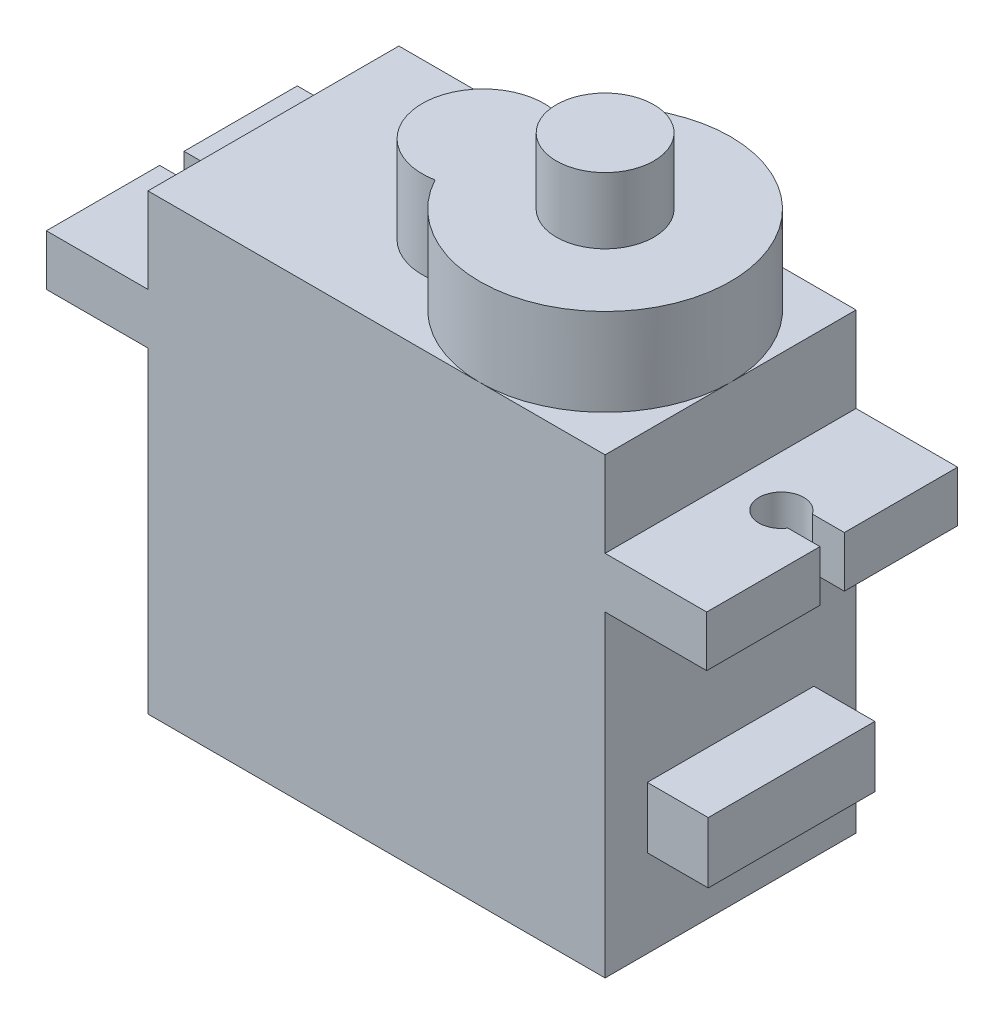
SolidWorks part; units mm, degrees
ref_plane "Front Plane" through (0, 0, 0) normal (0, 0, 1) x (1, 0, 0)
ref_plane "Top Plane" through (0, 0, 0) normal (0, 1, 0) x (1, 0, 0)
ref_plane "Right Plane" through (0, 0, 0) normal (1, 0, 0) x (0, 0, -1)
sketch "Sketch1" plane through (0, 0, 0) normal (0, 0, 1) x (1, 0, 0)
  line L0 (0, 0) -> (22.5, 0)
  line L1 (22.5, 0) -> (22.5, 15.6)
  line L2 (22.5, 18.1) -> (27.5, 18.1)
  line L3 (27.5, 18.1) -> (27.5, 15.6)
  line L4 (27.5, 15.6) -> (22.5, 15.6)
  line L5 (22.5, 18.1) -> (22.5, 22.3)
  line L6 (22.5, 22.3) -> (0, 22.3)
  line L7 (0, 22.3) -> (0, 18.1)
  line L8 (0, 18.1) -> (-5, 18.1)
  line L9 (-5, 18.1) -> (-5, 15.6)
  line L10 (-5, 15.6) -> (0, 15.6)
  line L11 (0, 15.6) -> (0, 0)
  dimension "D1" = 22.3
  dimension "D2" = 15.6
  dimension "D3" = 2.5
  dimension "D4" = 5
  dimension "D5" = 5
  dimension "D6" = 2.5
  dimension "D7" = 15.6
  dimension "D8" = 22.5
  dimension "D9" = 22.5
extrude "Boss-Extrude1" add sketch "Sketch1" along normal blind 12.35
sketch "Sketch2" plane through (0, 22.3, 0) normal (0, 1, 0) x (1, 0, 0)
  line L0 (22.5, -12.35) -> (22.5, 0) construction
  line L1 (22.5, 0) -> (0, 0) construction
  line L2 (22.5, -12.35) -> (0, -12.35) construction
  line L3 (0, -6.175) -> (22.5, -6.175) construction
  line L4 (0, -12.35) -> (0, 0) construction
  arc A0 (10.8974, -9.1199) -> (10.8974, -3.2301) centre (16.325, -6.175) ccw
  arc A1 (10.8974, -3.2301) -> (10.8974, -9.1199) centre (10.325, -6.175) ccw
  point P10 (0, 0)
  dimension "D2" = 6
  dimension "D1" = 6
extrude "Boss-Extrude2" add sketch "Sketch2" along normal blind 4.3
sketch "Sketch3" plane through (0, 26.6, 0) normal (0, 1, 0) x (1, 0, 0)
  circle A0 centre (16.325, -6.175) radius 2.4
  dimension "D1" = 4.8
extrude "Boss-Extrude3" add sketch "Sketch3" along normal blind 3.25
sketch "Sketch4" plane through (22.5, 0, 0) normal (1, 0, 0) x (0, 0, -1)
  line L0 (-12.35, 0) -> (0, 0) construction
  line L1 (-10.275, 7.3) -> (-2.075, 7.3)
  line L2 (-10.275, 7.3) -> (-10.275, 4.3)
  line L3 (-10.275, 4.3) -> (-2.075, 4.3)
  line L4 (-2.075, 7.3) -> (-2.075, 4.3)
  line L5 (-6.175, 15.6) -> (-6.175, 0) construction
  line L6 (-12.35, 15.6) -> (0, 15.6) construction
  line L7 (-6.175, 7.3) -> (-6.175, 4.3) construction
  dimension "D1" = 4.3
  dimension "D2" = 8.2
  dimension "D3" = 3
extrude "Boss-Extrude4" add sketch "Sketch4" along normal blind 3
sketch "Sketch5" plane through (0, 18.1, 0) normal (0, 1, 0) x (1, 0, 0)
  line L0 (27.5, -12.35) -> (22.5, -12.35) construction
  line L1 (27.5, -12.35) -> (27.5, 0) construction
  line L2 (-5, -12.35) -> (-5, 0) construction
  line L3 (0, -12.35) -> (-5, -12.35) construction
  line L4 (-3.6, -6.175) -> (-5, -6.175) construction
  line L5 (-3.422, -5.575) -> (-5, -5.575)
  line L6 (-3.422, -6.775) -> (-5, -6.775)
  line L7 (-5, -5.575) -> (-5, -6.775)
  line L8 (25, -6.175) -> (27.5, -6.175) construction
  line L9 (25.922, -6.775) -> (27.5, -6.775)
  line L10 (27.5, -5.575) -> (25.922, -5.575)
  line L11 (27.5, -5.575) -> (27.5, -6.775)
  arc A0 (25.922, -5.575) -> (25.922, -6.775) centre (25, -6.175) ccw
  arc A1 (-3.422, -6.775) -> (-3.422, -5.575) centre (-2.5, -6.175) ccw
  dimension "D1" = 2.2
  dimension "D4" = 2.2
  dimension "D2" = 6.175
  dimension "D3" = 2.5
  dimension "D5" = 2.5
  dimension "D6" = 6.175
  dimension "D7" = 0.6
  dimension "D8" = 0.6
  dimension "D9" = 0.6
  dimension "D10" = 0.6
extrude "Cut-Extrude1" cut sketch "Sketch5" against normal blind 3
